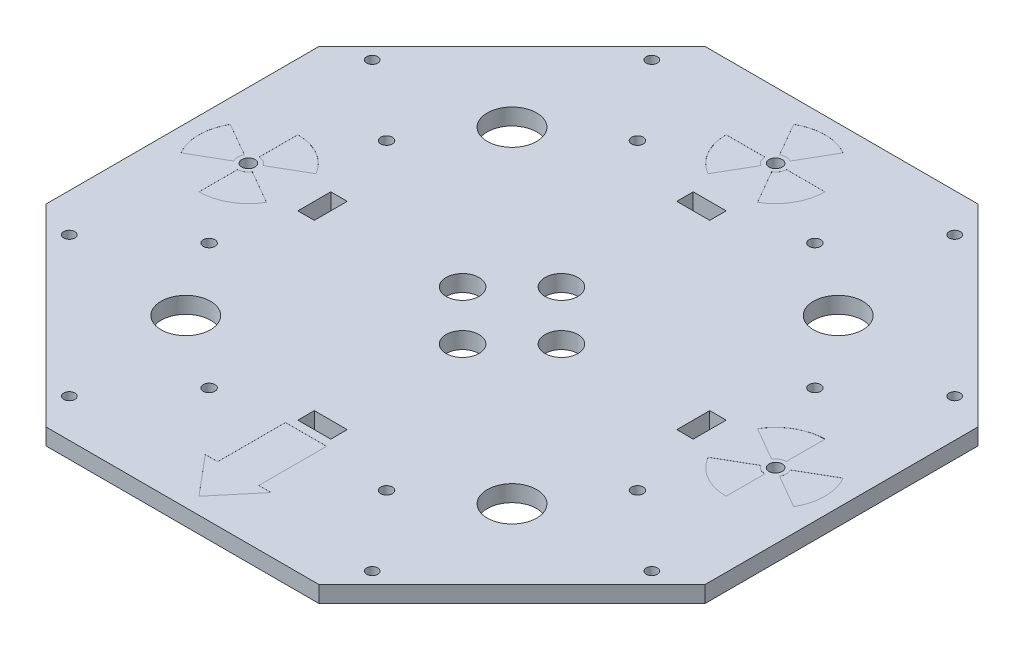
SolidWorks part; units mm, degrees
material "Custom Plastic"
ref_plane "Front Plane" through (0, 0, 0) normal (0, 0, 1) x (1, 0, 0)
ref_plane "Top Plane" through (0, 0, 0) normal (0, 1, 0) x (1, 0, 0)
ref_plane "Right Plane" through (0, 0, 0) normal (1, 0, 0) x (0, 0, -1)
ref_axis "Axis1" through (0, -0.2997, 0) along (0, 1, 0)
sketch "Base sketch" plane through (0, 0, 0) normal (0, 1, 0) x (1, 0, 0)
  line L1 (-127, 52.6051) -> (-127, -52.6051)
  line L2 (-127, -52.6051) -> (-52.6051, -127)
  line L3 (-52.6051, -127) -> (52.6051, -127)
  line L4 (52.6051, -127) -> (127, -52.6051)
  line L5 (127, -52.6051) -> (127, 52.6051)
  line L6 (127, 52.6051) -> (52.6051, 127)
  line L7 (52.6051, 127) -> (-52.6051, 127)
  line L8 (-52.6051, 127) -> (-127, 52.6051)
  circle A0 centre (0, 0) radius 127 construction
  dimension "D1" = 254
extrude "Base" add sketch "Base sketch" along normal blind 6.35
sketch "Sketch3" plane through (0, 6.35, 0) normal (0, 1, 0) x (1, 0, 0)
  line L0 (52.6051, 127) -> (-52.6051, 127) construction
  line L1 (-34.925, 114.3) -> (34.925, 114.3)
  line L2 (-34.925, 114.3) -> (-34.925, 79.375)
  line L4 (-34.925, 79.375) -> (34.925, 79.375)
  line L5 (34.925, 114.3) -> (34.925, 79.375)
  point P6 (0, 79.375)
  dimension "D1" = 69.85
  dimension "D2" = 34.925
  dimension "D3" = 12.7
sketch "Sketch4" plane through (0, 6.35, 0) normal (0, 1, 0) x (1, 0, 0)
  line L0 (0, 0) -> (0, 127) construction
  line L1 (52.6051, 127) -> (-52.6051, 127) construction
  line L4 (-6.35, 69.85) -> (6.35, 69.85)
  line L5 (-6.35, 69.85) -> (-6.35, 76.2)
  line L6 (-6.35, 76.2) -> (6.35, 76.2)
  line L7 (6.35, 69.85) -> (6.35, 76.2)
  line L8 (-6.35, 69.85) -> (6.35, 76.2) construction
  line L10 (-6.35, 76.2) -> (6.35, 69.85) construction
  point P5 (0, 73.025)
  dimension "D1" = 6.35
  dimension "D2" = 12.7
  dimension "D3" = 53.975
extrude "Support cutouts" cut sketch "Sketch4" against normal up to next
pattern_circular "Support cutout pattern" count 4 over 360 about axis through (0, -0.2997, 0) along (0, 1, 0) of "Support cutouts"
sketch "Sketch11" plane through (0, 6.35, 0) normal (0, 1, 0) x (1, 0, 0)
  line L1 (95.25, 39.4538) -> (39.4538, 95.25) construction
  line L2 (39.4538, 95.25) -> (-39.4538, 95.25) construction
  line L3 (-39.4538, 95.25) -> (-95.25, 39.4538) construction
  line L4 (-95.25, 39.4538) -> (-95.25, -39.4538) construction
  line L5 (-95.25, -39.4538) -> (-39.4538, -95.25) construction
  line L6 (-39.4538, -95.25) -> (39.4538, -95.25) construction
  line L7 (39.4538, -95.25) -> (95.25, -39.4538) construction
  line L8 (95.25, -39.4538) -> (95.25, 39.4538) construction
  line L9 (-34.1933, 82.55) -> (-82.55, 34.1933)
  line L10 (-82.55, 34.1933) -> (-82.55, -34.1933)
  line L11 (-82.55, -34.1933) -> (-34.1933, -82.55)
  line L12 (-34.1933, -82.55) -> (34.1933, -82.55)
  line L13 (34.1933, -82.55) -> (82.55, -34.1933)
  line L14 (82.55, -34.1933) -> (82.55, 34.1933)
  line L15 (82.55, 34.1933) -> (34.1933, 82.55)
  line L16 (34.1933, 82.55) -> (-34.1933, 82.55)
  circle A0 centre (0, 0) radius 95.25 construction
  circle A1 centre (0, 0) radius 82.55 construction
  dimension "D1" = 190.5
  dimension "D2" = 12.7
hole_wizard "#8 Clearance Hole1" positions "Sketch13" profile "Sketch12" hole size "#8" standard "ANSI Inch" end condition through all
sketch "Sketch13" plane through (0, 6.35, 0) normal (0, 1, 0) x (1, 0, 0)
  point P0 (-82.55, 34.1933)
  point P3 (-34.1933, 82.55)
  point P6 (34.1933, 82.55)
  point P9 (82.55, 34.1933)
  point P12 (82.55, -34.1933)
  point P15 (34.1933, -82.55)
  point P18 (-34.1933, -82.55)
  point P21 (-82.55, -34.1933)
sketch "Sketch12" plane through (-82.55, 6.35, -34.1933) normal (1, 0, 0) x (0, 0, 1)
  line L0 (0, 0) -> (0, 6.35)
  line L1 (0, 6.35) -> (2.2479, 6.35)
  line L2 (2.2479, 6.35) -> (2.2479, 0)
  line L5 (2.2479, 0) -> (0, 0)
  line L11 (0, -6.35) -> (0, 107.95) construction
  dimension "Thru Hole Dia." = 4.4958
  dimension "Thru Hole Depth" = 6.35
sketch "Sketch14" plane through (0, 6.35, 0) normal (0, 1, 0) x (1, 0, 0)
  circle A0 centre (-62.8618, 62.8618) radius 9.525
  circle A1 centre (62.8618, 62.8618) radius 9.525
  circle A2 centre (62.8618, -62.8618) radius 9.525
  circle A3 centre (-62.8618, -62.8618) radius 9.525
  point P13 (0, 0)
  dimension "D2" = 19.05
  dimension "D1" = 88.9
  dimension "D3" = 4
extrude "Cable holes" cut sketch "Sketch14" against normal up to next
sketch "Sketch18" plane through (0, 6.35, 0) normal (0, 1, 0) x (1, 0, 0)
  line L0 (89.8026, 89.8026) -> (0, 0) construction
  line L1 (127, 52.6051) -> (52.6051, 127) construction
  line L2 (58.3717, 112.2532) -> (112.2532, 58.3717) construction
  point P7 (85.3124, 85.3124)
  dimension "D1" = 76.2
  dimension "D2" = 6.35
hole_wizard "plate mounting holes" positions "Sketch20" profile "Sketch19" hole size "#8" standard "ANSI Inch"
sketch "Sketch20" plane through (0, 6.35, 0) normal (0, 1, 0) x (1, 0, 0)
  point P0 (112.2532, 58.3717)
  point P7 (58.3717, 112.2532)
sketch "Sketch19" plane through (112.2532, 6.35, -58.3717) normal (1, 0, 0) x (0, 0, 1)
  line L0 (0, 0) -> (0, 6.351)
  line L1 (0, 6.351) -> (2.1526, 6.351)
  line L2 (2.1526, 6.351) -> (2.1526, 0)
  line L5 (2.1526, 0) -> (0, 0)
  line L10 (0, 6.351) -> (-2.1527, 6.351) construction
  line L11 (0, -6.35) -> (0, 107.95) construction
  dimension "Hole Dia." = 4.3053
  dimension "Hole Depth" = 6.351
  dimension "Drill Angle" = 180
pattern_circular "CirPattern1" count 4 over 360 about axis through (0, -0.2997, 0) along (0, 1, 0) of "plate mounting holes"
sketch "Sketch21" plane through (0, 6.35, 0) normal (0, 1, 0) x (1, 0, 0)
  line L0 (0, 0) -> (0, 19.05) construction
  circle A0 centre (0, 19.05) radius 6.35
  dimension "D2" = 12.7
  dimension "D1" = 19.05
extrude "Cut-Extrude1" cut sketch "Sketch21" against normal through all
pattern_circular "CirPattern2" count 4 over 360 about axis through (0, -0.2997, 0) along (0, 1, 0) of "Cut-Extrude1"
sketch "Sketch22" plane through (0, 6.35, 0) normal (0, 1, 0) x (1, 0, 0)
  line L0 (0, -127) -> (0, 0) construction
  line L1 (-52.6051, -127) -> (52.6051, -127) construction
  line L2 (0, -120.65) -> (-12.7, -105.5147)
  line L3 (-12.7, -105.5147) -> (-7.9375, -105.5147)
  line L4 (-7.9375, -105.5147) -> (-7.9375, -79.375)
  line L5 (-7.9375, -79.375) -> (7.9375, -79.375)
  line L6 (7.9375, -79.375) -> (7.9375, -105.5147)
  line L7 (7.9375, -105.5147) -> (12.7, -105.5147)
  line L8 (12.7, -105.5147) -> (0, -120.65)
  line L9 (-6.35, -76.2) -> (6.35, -76.2) construction
  dimension "D1" = 25.4
  dimension "D2" = 15.875
  dimension "D3" = 40
  dimension "D4" = 6.35
  dimension "D5" = 3.175
extrude "Arrow" cut sketch "Sketch22" against normal blind 0.0254
sketch "Sketch23" plane through (0, 6.35, 0) normal (0, 1, 0) x (1, 0, 0)
  line L0 (76.2, 0) -> (127, 0) construction
  line L1 (76.2, -6.35) -> (76.2, 6.35) construction
  line L2 (127, -52.6051) -> (127, 52.6051) construction
  line L3 (105.1745, -2.0638) -> (118.0978, -9.525)
  line L5 (118.0978, 9.525) -> (105.1745, 2.0638)
  line L6 (98.0255, -2.0638) -> (85.1022, -9.525)
  line L8 (101.6, -19.05) -> (101.6, -4.1275)
  line L9 (98.0255, 2.0638) -> (85.1022, 9.525)
  line L11 (101.6, 19.05) -> (101.6, 4.1275)
  circle A0 centre (101.6, 0) radius 19.05 construction
  circle A1 centre (101.6, 0) radius 2.54
  arc A2 (105.1745, -2.0638) -> (105.1745, 2.0638) centre (101.6, 0) ccw
  arc A3 (98.0255, -2.0638) -> (101.6, -4.1275) centre (101.6, 0) ccw
  arc A4 (101.6, 4.1275) -> (98.0255, 2.0638) centre (101.6, 0) ccw
  arc A5 (85.1022, 9.525) -> (101.6, 19.05) centre (101.6, 0) cw
  arc A6 (118.0978, 9.525) -> (118.0978, -9.525) centre (101.6, 0) cw
  arc A7 (85.1022, -9.525) -> (101.6, -19.05) centre (101.6, 0) ccw
  dimension "D1" = 38.1
  dimension "D2" = 5.08
  dimension "D3" = 1.5875
  dimension "D4" = 60
  dimension "D5" = 60
extrude "Radiation symbol" cut sketch "Sketch23" against normal blind 0.0254
sketch "Sketch25" plane through (0, 6.35, 0) normal (0, 1, 0) x (1, 0, 0)
  circle A0 centre (101.6, 0) radius 2.54
extrude "Radiation symbol LED hole" cut sketch "Sketch25" against normal through all
pattern_circular "CirPattern3" count 3 every 90 about axis through (0, -0.2997, 0) along (0, 1, 0) of "Radiation symbol", "Radiation symbol LED hole"
equation "\"MAT_THICKNESS\"=0.25"
equation "\"D1@Base\"=\"MAT_THICKNESS\""
equation "\"D1@Sketch4\"=\"MAT_THICKNESS\""
